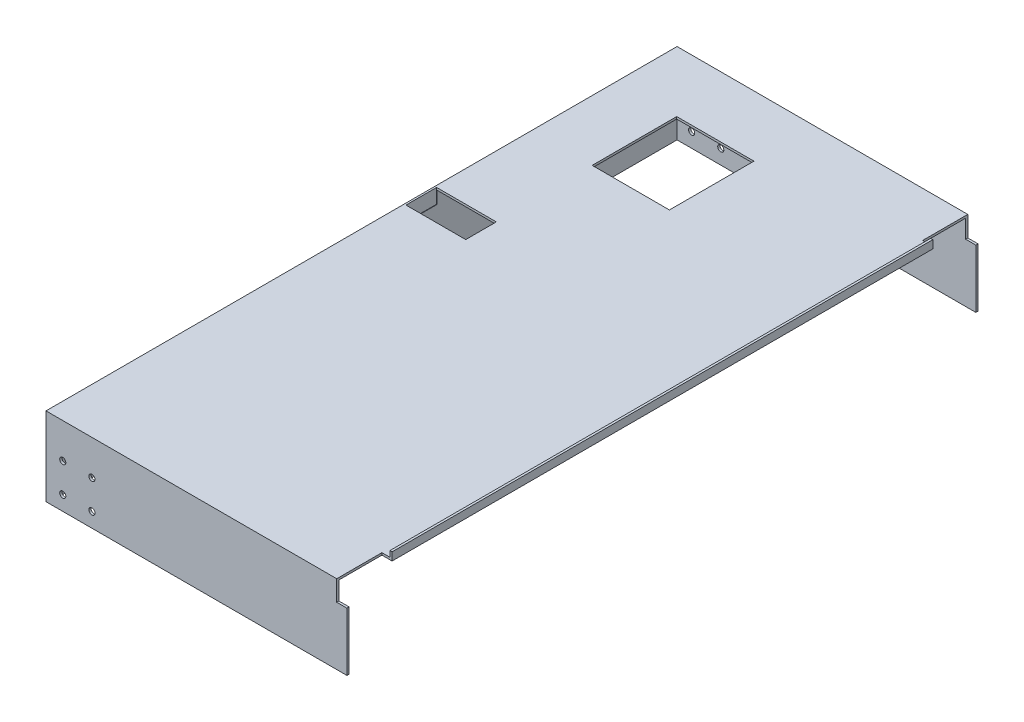
SolidWorks part; units mm, degrees
ref_plane "Front Plane" through (0, 0, 0) normal (0, 0, 1) x (1, 0, 0)
ref_plane "Top Plane" through (0, 0, 0) normal (0, 1, 0) x (1, 0, 0)
ref_plane "Right Plane" through (0, 0, 0) normal (1, 0, 0) x (0, 0, -1)
sketch "Sketch4" plane through (0, 0, 0) normal (0, 1, 0) x (1, 0, 0)
  line L0 (124.0135, 430) -> (329.0135, 430)
  line L1 (329.0135, 430) -> (329.0135, 0)
  line L2 (329.0135, 0) -> (124.0135, 0)
  line L3 (124.0135, 0) -> (124.0135, 200)
  line L7 (124.0135, 365) -> (124.0135, 430)
  line L8 (124.0135, 200) -> (124.0135, 365)
  line L9 (329.0135, 80.0946) -> (329.0135, 106.0946) construction
  dimension "D2" = 65
  dimension "D4" = 200
  dimension "D5" = 205
  dimension "D6" = 205
extrude "Boss-Extrude4" add sketch "Sketch4" along normal blind 1.5 separate body
sketch "Sketch5" plane through (0, 0, 0) normal (0, 0, 1) x (1, 0, 0)
  line L1 (124.0135, 1.5) -> (329.0135, 1.5)
  line L2 (124.0135, 1.5) -> (124.0135, -52.5)
  line L3 (124.0135, -52.5) -> (329.0135, -52.5)
  line L4 (329.0135, 1.5) -> (329.0135, -52.5)
  dimension "D1" = 54
sketch "Sketch7" plane through (0, 0, -430) normal (0, 0, -1) x (-1, 0, 0)
  line L1 (-124.0135, 1.5) -> (-329.0135, 1.5)
  line L2 (-124.0135, 1.5) -> (-124.0135, -52.5)
  line L3 (-124.0135, -52.5) -> (-329.0135, -52.5)
  line L4 (-329.0135, 1.5) -> (-329.0135, -52.5)
  dimension "D1" = 54
  dimension "D2" = 205
sketch "Sketch8" plane through (0, 1.5, 0) normal (0, 1, 0) x (1, 0, 0)
  line L0 (124.0135, 430) -> (329.0135, 430) construction
  line L1 (329.0135, 0) -> (327.5135, 0)
  line L2 (329.0135, 0) -> (329.0135, 430)
  line L3 (329.0135, 430) -> (327.5135, 430)
  line L4 (327.5135, 0) -> (327.5135, 430)
  dimension "D1" = 1.5
extrude "Boss-Extrude5" add sketch "Sketch5" along normal blind 1.5
extrude "Boss-Extrude14" add sketch "Sketch8" along normal blind 4
extrude "Boss-Extrude18" add sketch "Sketch7" along normal blind 1.5
sketch "Sketch9" plane through (124.0135, 0, 0) normal (-1, 0, 0) x (0, 0, 1)
  line L1 (-431.5, 1.5) -> (1.5, 1.5)
  line L2 (-431.5, 1.5) -> (-431.5, -52.5)
  line L3 (-431.5, -52.5) -> (1.5, -52.5)
  line L4 (1.5, 1.5) -> (1.5, -52.5)
extrude "Boss-Extrude19" add sketch "Sketch9" along normal blind 1.5
sketch "Sketch10" plane through (0, 0, -431.5) normal (0, 0, -1) x (-1, 0, 0)
  circle A0 centre (-154.0135, -42.5) radius 2.1
sketch "Sketch11" plane through (0, 0, -431.5) normal (0, 0, -1) x (-1, 0, 0)
  circle A0 centre (-134.0237, -42.5218) radius 2.1
sketch "Sketch12" plane through (0, 0, -431.5) normal (0, 0, -1) x (-1, 0, 0)
  circle A0 centre (-134.0173, -22.4773) radius 2.1
sketch "Sketch13" plane through (0, 0, -431.5) normal (0, 0, -1) x (-1, 0, 0)
  circle A0 centre (-154.0032, -22.5144) radius 2.1
sketch "Sketch14" plane through (0, 0, 1.5) normal (0, 0, 1) x (1, 0, 0)
  circle A0 centre (134.0173, -22.4773) radius 2.1
sketch "Sketch15" plane through (0, 0, 1.5) normal (0, 0, 1) x (1, 0, 0)
  circle A0 centre (154.0032, -22.5144) radius 2.1
sketch "Sketch16" plane through (0, 0, 1.5) normal (0, 0, 1) x (1, 0, 0)
  circle A0 centre (134.0237, -42.5218) radius 2.1
sketch "Sketch17" plane through (0, 0, 1.5) normal (0, 0, 1) x (1, 0, 0)
  circle A0 centre (154.0135, -42.5) radius 2.1
extrude "Cut-Extrude1" cut sketch "Sketch10" against normal blind 10
extrude "Cut-Extrude2" cut sketch "Sketch17" against normal blind 10
extrude "Cut-Extrude3" cut sketch "Sketch16" against normal blind 10
extrude "Cut-Extrude4" cut sketch "Sketch11" against normal blind 10
extrude "Cut-Extrude5" cut sketch "Sketch12" against normal blind 10
extrude "Cut-Extrude6" cut sketch "Sketch13" against normal blind 10
extrude "Cut-Extrude7" cut sketch "Sketch14" against normal blind 10
extrude "Cut-Extrude8" cut sketch "Sketch15" against normal blind 10
sketch "Sketch18" plane through (0, 1.5, 0) normal (0, 1, 0) x (1, 0, 0)
  line L1 (123.7353, 265.2813) -> (164.7353, 265.2813)
  line L2 (123.7353, 265.2813) -> (123.7353, 244.2776)
  line L3 (123.7353, 244.2776) -> (164.7353, 244.2776)
  line L4 (164.7353, 265.2813) -> (164.7353, 244.2776)
  dimension "D1" = 41
extrude "Cut-Extrude9" cut sketch "Sketch18" against normal blind 10
sketch "Sketch21" plane through (0, 1.5, 0) normal (0, 1, 0) x (1, 0, 0)
  line L1 (164.0135, 389.7654) -> (217.0135, 389.7654)
  line L2 (164.0135, 389.7654) -> (164.0135, 331.7654)
  line L3 (164.0135, 331.7654) -> (217.0135, 331.7654)
  line L4 (217.0135, 389.7654) -> (217.0135, 331.7654)
extrude "Cut-Extrude12" cut sketch "Sketch21" against normal blind 10
sketch "Sketch23" plane through (0, 0, 1.5) normal (0, 0, 1) x (1, 0, 0)
  line L0 (329.0135, -52.5) -> (329.0135, 1.5) construction
  line L1 (322.0135, 5.5) -> (329.0135, 5.5)
  line L2 (322.0135, 5.5) -> (322.0135, -12.5)
  line L3 (322.0135, -12.5) -> (329.0135, -12.5)
  line L4 (329.0135, 5.5) -> (329.0135, -12.5)
  point P6 (329.0135, 5.5)
extrude "Cut-Extrude14" cut sketch "Sketch23" against normal blind 31
sketch "Sketch24" plane through (0, 0, -431.5) normal (0, 0, -1) x (-1, 0, 0)
  line L1 (-329.0135, 5.5) -> (-322.0135, 5.5)
  line L2 (-329.0135, 5.5) -> (-329.0135, -12.5)
  line L3 (-329.0135, -12.5) -> (-322.0135, -12.5)
  line L4 (-322.0135, 5.5) -> (-322.0135, -12.5)
extrude "Cut-Extrude15" cut sketch "Sketch24" against normal blind 31
